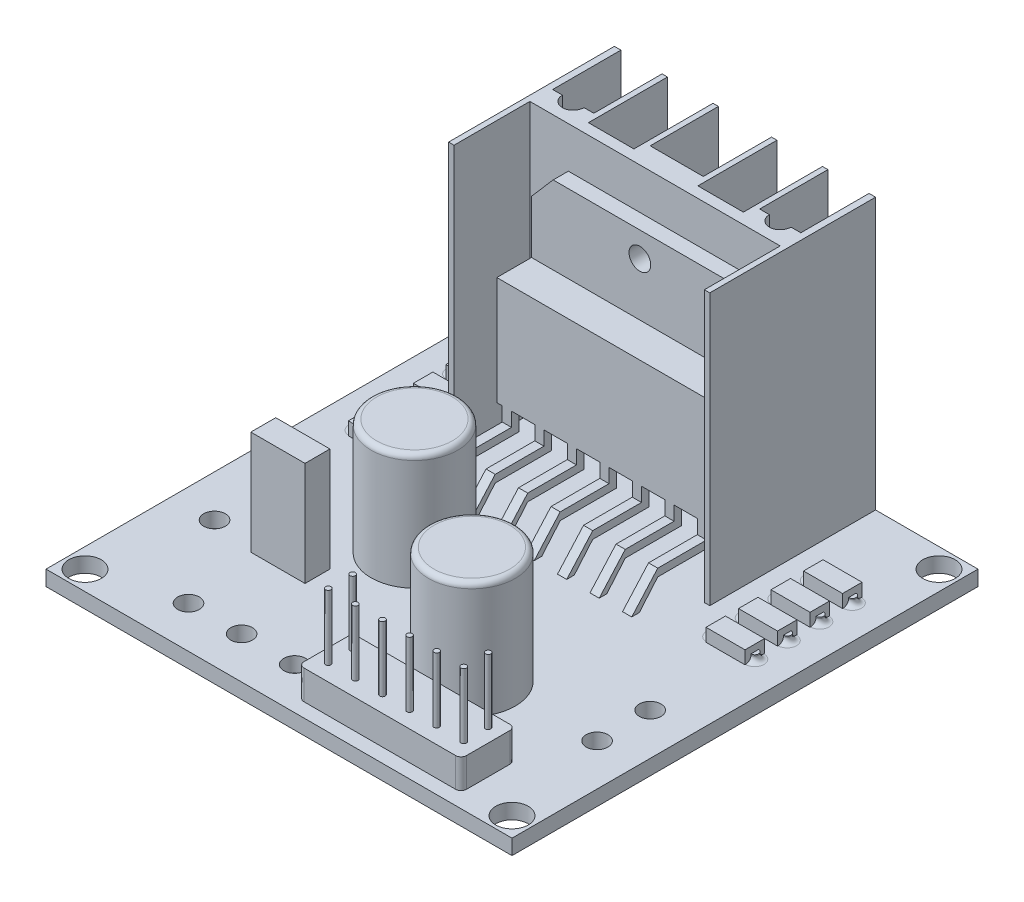
SolidWorks part; units mm, degrees
ref_plane "Alzado" through (0, 0, 0) normal (0, 0, 1) x (1, 0, 0)
ref_plane "Planta" through (0, 0, 0) normal (0, 1, 0) x (1, 0, 0)
ref_plane "Vista lateral" through (0, 0, 0) normal (1, 0, 0) x (0, 0, -1)
sketch "Croquis1" plane through (0, 0, 0) normal (0, 1, 0) x (1, 0, 0)
  line L1 (-21.5, 21.5) -> (21.5, 21.5)
  line L2 (-21.5, 21.5) -> (-21.5, -21.5)
  line L3 (-21.5, -21.5) -> (21.5, -21.5)
  line L4 (21.5, 21.5) -> (21.5, -21.5)
  line L5 (-21.5, 21.5) -> (21.5, -21.5) construction
  line L6 (-21.5, -21.5) -> (21.5, 21.5) construction
  circle A0 centre (19.7, 19.7) radius 1.5
  circle A1 centre (-19.7, 19.7) radius 1.5
  circle A2 centre (-19.7, -19.7) radius 1.5
  circle A3 centre (19.7, -19.7) radius 1.5
  point P1 (0, 0)
  point P8 (0, 0)
  point P9 (0, 0)
  dimension "D3" = 3
  dimension "D1" = 43
  dimension "D2" = 43
  dimension "D4" = 1.8
  dimension "D5" = 1.8
  dimension "D8" = 1.8
  dimension "D9" = 1.8
  dimension "D6" = 2
  dimension "D7" = 2
extrude "Saliente-Extruir1" add sketch "Croquis1" along normal blind 1.4
sketch "Croquis2" plane through (0, 1.4, 0) normal (0, 1, 0) x (1, 0, 0)
  line L0 (21.5, -21.5) -> (21.5, 21.5) construction
  line L1 (-21.5, -21.5) -> (21.5, -21.5) construction
  line L2 (-21.5, 21.5) -> (-21.5, -21.5) construction
  circle A0 centre (7.1, -10.8) radius 4
  circle A1 centre (-5.8, -3.2) radius 4
  point P8 (0, 0)
  dimension "D1" = 8
  dimension "D6" = 8
  dimension "D2" = 14.4
  dimension "D3" = 10.7
  dimension "D4" = 18.3
  dimension "D5" = 15.7
extrude "Saliente-Extruir2" add sketch "Croquis2" along normal blind 10.7
fillet "Redondeo1" radius 0.5 2 edges at (7.1, 12.1, 14.8) (-5.8, 12.1, 7.2)
sketch "Croquis3" plane through (0, 1.4, 0) normal (0, 1, 0) x (1, 0, 0)
  line L0 (-21.5, 21.5) -> (-21.5, -21.5) construction
  line L1 (21.5, -21.5) -> (21.5, 21.5) construction
  line L2 (-21.5, -21.5) -> (21.5, -21.5) construction
  circle A0 centre (-17.65, -4.9) radius 1
  circle A1 centre (-17.65, -9.8) radius 1
  circle A2 centre (-12.2, -17.65) radius 1
  circle A3 centre (-7.3, -17.65) radius 1
  circle A4 centre (-2.4, -17.65) radius 1
  circle A5 centre (17.65, -4.9) radius 1
  circle A6 centre (17.65, -9.8) radius 1
  point P16 (0, 0)
  point P19 (0, 0)
  point P20 (0, 0)
  point P21 (0, 0)
  point P24 (0, 0)
  point P25 (0, 0)
  dimension "D2" = 2
  dimension "D3" = 2
  dimension "D6" = 2
  dimension "D7" = 2
  dimension "D8" = 2
  dimension "D9" = 2
  dimension "D10" = 2
  dimension "D1" = 3.85
  dimension "D4" = 4.9
  dimension "D5" = 3.85
  dimension "D11" = 4.9
  dimension "D12" = 4.9
  dimension "D13" = 3.85
  dimension "D14" = 19.1
  dimension "D15" = 11.7
extrude "Cortar-Extruir1" cut sketch "Croquis3" against normal up to surface (1.4 mm away) up to face at (0, 0, 0)
sketch "Croquis4" plane through (0, 1.4, 0) normal (0, 1, 0) x (1, 0, 0)
  line L0 (-21.5, -21.5) -> (21.5, -21.5) construction
  line L1 (-13.4, -8.4) -> (-8.4, -8.4)
  line L2 (-13.4, -8.4) -> (-13.4, -10.7)
  line L3 (-13.4, -10.7) -> (-8.4, -10.7)
  line L4 (-8.4, -8.4) -> (-8.4, -10.7)
  line L5 (-13.4, -8.4) -> (-8.4, -10.7) construction
  line L6 (-13.4, -10.7) -> (-8.4, -8.4) construction
  line L7 (-21.5, 21.5) -> (-21.5, -21.5) construction
  point P0 (-10.9, -9.55)
  dimension "D1" = 13.1
  dimension "D2" = 2.3
  dimension "D3" = 5
  dimension "D4" = 8.1
extrude "Saliente-Extruir3" add sketch "Croquis4" along normal blind 9.6
sketch "Croquis5" plane through (0, 1.4, 0) normal (0, 1, 0) x (1, 0, 0)
  line L0 (-21.5, -21.5) -> (21.5, -21.5) construction
  line L1 (0.5, -15.2) -> (15.5, -15.2)
  line L2 (0.5, -15.2) -> (0.5, -20.2)
  line L3 (0.5, -20.2) -> (15.5, -20.2)
  line L4 (15.5, -15.2) -> (15.5, -20.2)
  line L5 (0.5, -15.2) -> (15.5, -20.2) construction
  line L6 (0.5, -20.2) -> (15.5, -15.2) construction
  line L7 (21.5, -21.5) -> (21.5, 21.5) construction
  point P0 (8, -17.7)
  dimension "D1" = 15
  dimension "D2" = 5
  dimension "D3" = 1.3
  dimension "D4" = 6
extrude "Saliente-Extruir4" add sketch "Croquis5" along normal blind 2.7
fillet "Redondeo2" radius 0.5 4 edges at (0.5, 2.75, 15.2) (0.5, 2.75, 20.2) (15.5, 2.75, 20.2) (15.5, 2.75, 15.2)
sketch "Croquis6" plane through (0, 4.1, 0) normal (0, 1, 0) x (1, 0, 0)
  line L1 (15, -15.2) -> (1, -15.2) construction
  line L2 (1, -20.2) -> (15, -20.2) construction
  line L3 (0.5, -15.7) -> (0.5, -19.7) construction
  circle A0 centre (1.75, -16.45) radius 0.25
  circle A1 centre (1.75, -18.7) radius 0.25
  circle A2 centre (4.25, -18.7) radius 0.25
  circle A3 centre (6.75, -18.7) radius 0.25
  circle A4 centre (9.25, -18.7) radius 0.25
  circle A5 centre (11.75, -18.7) radius 0.25
  circle A6 centre (14.25, -18.7) radius 0.25
  circle A7 centre (14.25, -16.45) radius 0.25
  point P22 (0, 0)
  point P23 (0, 0)
  point P24 (0, 0)
  point P25 (0, 0)
  point P26 (0, 0)
  point P27 (0, 0)
  point P28 (0, 0)
  point P29 (0, 0)
  point P30 (0, 0)
  point P31 (0, 0)
  dimension "D1" = 0.5
  dimension "D2" = 0.5
  dimension "D3" = 0.5
  dimension "D4" = 0.5
  dimension "D5" = 0.5
  dimension "D6" = 0.5
  dimension "D7" = 0.5
  dimension "D8" = 0.5
  dimension "D9" = 1.25
  dimension "D10" = 1.5
  dimension "D11" = 1.25
  dimension "D12" = 2.5
  dimension "D13" = 2.5
  dimension "D14" = 2.5
  dimension "D15" = 2.5
  dimension "D16" = 2.5
extrude "Saliente-Extruir5" add sketch "Croquis6" along normal blind 6
sketch "Croquis7" plane through (0, 1.4, 0) normal (0, 1, 0) x (1, 0, 0)
  line L0 (21.5, 21.5) -> (-21.5, 21.5) construction
  line L1 (-18.2, 13.9) -> (-14.6, 13.9)
  line L2 (-18.2, 13.9) -> (-18.2, 12.1)
  line L3 (-18.2, 12.1) -> (-14.6, 12.1)
  line L4 (-14.6, 13.9) -> (-14.6, 12.1)
  line L5 (-18.2, 13.9) -> (-14.6, 12.1) construction
  line L6 (-18.2, 12.1) -> (-14.6, 13.9) construction
  line L7 (-21.5, 21.5) -> (-21.5, -21.5) construction
  circle A0 centre (-14.6, 13) radius 0.35
  circle A1 centre (-18.2, 13) radius 0.35
  point P0 (-16.4, 13)
  dimension "D5" = 0.7
  dimension "D6" = 0.7
  dimension "D1" = 1.8
  dimension "D2" = 3.6
  dimension "D3" = 7.6
  dimension "D4" = 3.3
extrude "Saliente-Extruir6" add sketch "Croquis7" along normal blind 1.2 contours A1 L2 L3 L4 A0 L1 | L4 A0 | L2 A1 region at (-16.4, 1.4, -13) region at (-18.0515, 1.4, -13) region at (-14.7485, 1.4, -13)
extrude "Saliente-Extruir7" add sketch "Croquis7<3>" along normal blind 0.6 contours L2 A1 | L4 A0 region at (-18.3485, 1.4, -13) region at (-14.4515, 1.4, -13)
sketch "Croquis7<3>" plane through (0, 1.4, 0) normal (0, 1, 0) x (1, 0, 0) same geometry as "Croquis7"
fillet "Redondeo3" radius 0.5 2 edges at (-14.25, 1.4, -13) (-18.55, 1.4, -13)
pattern_linear "MatrizL1" count 4 spacing 3 along (0, 0, 1) count 2 spacing 33 along (1, 0, 0) of "Saliente-Extruir6", "Saliente-Extruir7", "Redondeo3"
sketch "Croquis8" plane through (0, 1.4, 0) normal (0, 1, 0) x (1, 0, 0)
  line L0 (-12.05, 21.5) -> (-12.05, 6.2)
  line L1 (21.5, 21.5) -> (-21.5, 21.5) construction
  line L2 (-12.05, 21.5) -> (-11.45, 21.5)
  line L3 (-11.45, 21.5) -> (-11.45, 15.2)
  line L4 (-11.45, 15.2) -> (-10.55, 15.2)
  line L5 (-7.65, 15.2) -> (-7.65, 21.5)
  line L6 (-7.65, 21.5) -> (-7.15, 21.5)
  line L7 (-7.15, 21.5) -> (-7.15, 14.2)
  line L8 (-7.15, 14.2) -> (-2.95, 14.2)
  line L9 (-2.95, 14.2) -> (-2.95, 21.5)
  line L10 (-2.95, 21.5) -> (-2.45, 21.5)
  line L11 (-2.45, 21.5) -> (-2.45, 15.2)
  line L12 (-2.45, 15.2) -> (2.45, 15.2)
  line L13 (2.45, 15.2) -> (2.45, 21.5)
  line L14 (2.45, 21.5) -> (2.95, 21.5)
  line L15 (2.95, 21.5) -> (2.95, 14.2)
  line L16 (2.95, 14.2) -> (7.15, 14.2)
  line L17 (7.15, 14.2) -> (7.15, 21.5)
  line L18 (7.15, 21.5) -> (7.65, 21.5)
  line L19 (7.65, 21.5) -> (7.65, 15.2)
  line L20 (7.65, 15.2) -> (8.55, 15.2)
  line L21 (10.55, 15.2) -> (11.45, 15.2)
  line L22 (11.45, 15.2) -> (11.45, 21.5)
  line L23 (11.45, 21.5) -> (12.05, 21.5)
  line L24 (12.05, 21.5) -> (12.05, 6.2)
  line L25 (12.05, 6.2) -> (11.55, 6.2)
  line L26 (11.55, 6.2) -> (11.55, 13.2)
  line L27 (11.55, 13.2) -> (-11.55, 13.2)
  line L28 (-11.55, 13.2) -> (-11.55, 6.2)
  line L29 (-11.55, 6.2) -> (-12.05, 6.2)
  line L30 (-7.65, 15.2) -> (-8.55, 15.2)
  arc A0 (-10.55, 15.2) -> (-8.55, 15.2) centre (-9.55, 15.2) ccw
  arc A1 (8.55, 15.2) -> (10.55, 15.2) centre (9.55, 15.2) ccw
  point P28 (0, 0)
  point P37 (0, 0)
  point P38 (0, 0)
  point P39 (0, 0)
  point P40 (0, 13.2)
  dimension "D15" = 1
  dimension "D23" = 1
  dimension "D1" = 0.6
  dimension "D2" = 0.6
  dimension "D3" = 0.5
  dimension "D4" = 0.5
  dimension "D5" = 0.5
  dimension "D6" = 3.8
  dimension "D7" = 6.3
  dimension "D8" = 7.3
  dimension "D9" = 1
  dimension "D10" = 0.9
  dimension "D11" = 0.9
  dimension "D12" = 0.9
  dimension "D13" = 0.9
  dimension "D14" = 3.8
  dimension "D16" = 4.2
  dimension "D17" = 4.9
  dimension "D18" = 4.2
  dimension "D19" = 0.5
  dimension "D20" = 7
  dimension "D21" = 0.5
  dimension "D22" = 0.5
extrude "Saliente-Extruir8" add sketch "Croquis8" along normal blind 25
sketch "Croquis9" plane through (0, 0, -13.2) normal (0, 0, 1) x (1, 0, 0)
  line L0 (10, 15.4) -> (10, 20.3)
  line L1 (-10, 15.4) -> (10, 15.4)
  line L2 (-10, 15.4) -> (-10, 5.4)
  line L3 (-10, 5.4) -> (10, 5.4)
  line L4 (10, 15.4) -> (10, 5.4)
  line L5 (-10, 15.4) -> (10, 5.4) construction
  line L6 (-10, 5.4) -> (10, 15.4) construction
  line L7 (10, 20.3) -> (8, 22.6)
  line L8 (8, 22.6) -> (-8, 22.6)
  line L9 (-8, 22.6) -> (-10, 20.3)
  line L10 (-10, 20.3) -> (-10, 15.4)
  line L12 (11.55, 26.4) -> (11.55, 1.4) construction
  line L13 (-11.55, 26.4) -> (11.55, 26.4) construction
  circle A0 centre (0, 20.3) radius 1
  point P0 (0, 10.4)
  point P11 (0, 0)
  point P16 (0, 0)
  point P17 (0, 22.6)
  point P18 (0, 0)
  point P19 (0, 0)
  dimension "D5" = 2
  dimension "D1" = 20
  dimension "D2" = 10
  dimension "D3" = 1.55
  dimension "D4" = 11
  dimension "D6" = 16
  dimension "D7" = 4.9
  dimension "D8" = 7.2
extrude "Saliente-Extruir9" add sketch "Croquis9" along normal blind 4.6 contours L2 L1 L4 L3
extrude "Saliente-Extruir10" add sketch "Croquis9<3>" along normal blind 1.4 contours L9 L10 L1 L0 L7 L8 A0 region at (0, 18.8744, -13.2)
sketch "Croquis9<3>" plane through (0, 0, -13.2) normal (0, 0, 1) x (1, 0, 0) same geometry as "Croquis9"
extrude "Cortar-Extruir2" cut sketch "Croquis9<4>" against normal up to surface (2 mm away) contours A0 region at (0, 20.3, -13.2) up to face at (0, 13.9, -15.2)
sketch "Croquis9<4>" plane through (0, 0, -13.2) normal (0, 0, 1) x (1, 0, 0) same geometry as "Croquis9"
sketch "Croquis10" plane through (0, 0, 0) normal (1, 0, 0) x (0, 0, -1)
  line L0 (1.6984, 1.4) -> (2.3984, 1.4)
  line L2 (9.3, 5.4) -> (8.6, 5.4)
  line L3 (8.6, 5.4) -> (8.6, 4.1)
  line L4 (8.6, 4.1) -> (4.1, 4.1)
  line L5 (4.1, 4.1) -> (1.6984, 1.4)
  line L6 (2.3984, 1.4) -> (4.1, 3.4)
  line L7 (4.1, 3.4) -> (9.3, 3.4)
  line L8 (9.3, 3.4) -> (9.3, 5.4)
  line L10 (4.9, 1.4) -> (4.85, 1.4) construction
  point P2 (0, 0)
  point P3 (0, 0)
  point P9 (6.1495, 1.9238)
  point P10 (4.0845, 0)
  point P11 (0, 0)
  point P14 (6.287, 2.0418)
  point P15 (6.2952, 1.8575)
  point P16 (0, 0)
  point P17 (0, 0)
  point P18 (9.0778, 2)
  dimension "D1" = 0.7
  dimension "D2" = 4.5
  dimension "D3" = 0.7
  dimension "D4" = 0.7
  dimension "D5" = 2
  dimension "D6" = 1.261
extrude "Saliente-Extruir11" add sketch "Croquis10" along normal blind 0.35 and the other way blind 0.5
pattern_linear "MatrizL2" count 4 spacing 3 along (1, 0, 0) count 4 spacing 3 along (-1, 0, 0) of "Saliente-Extruir11"
